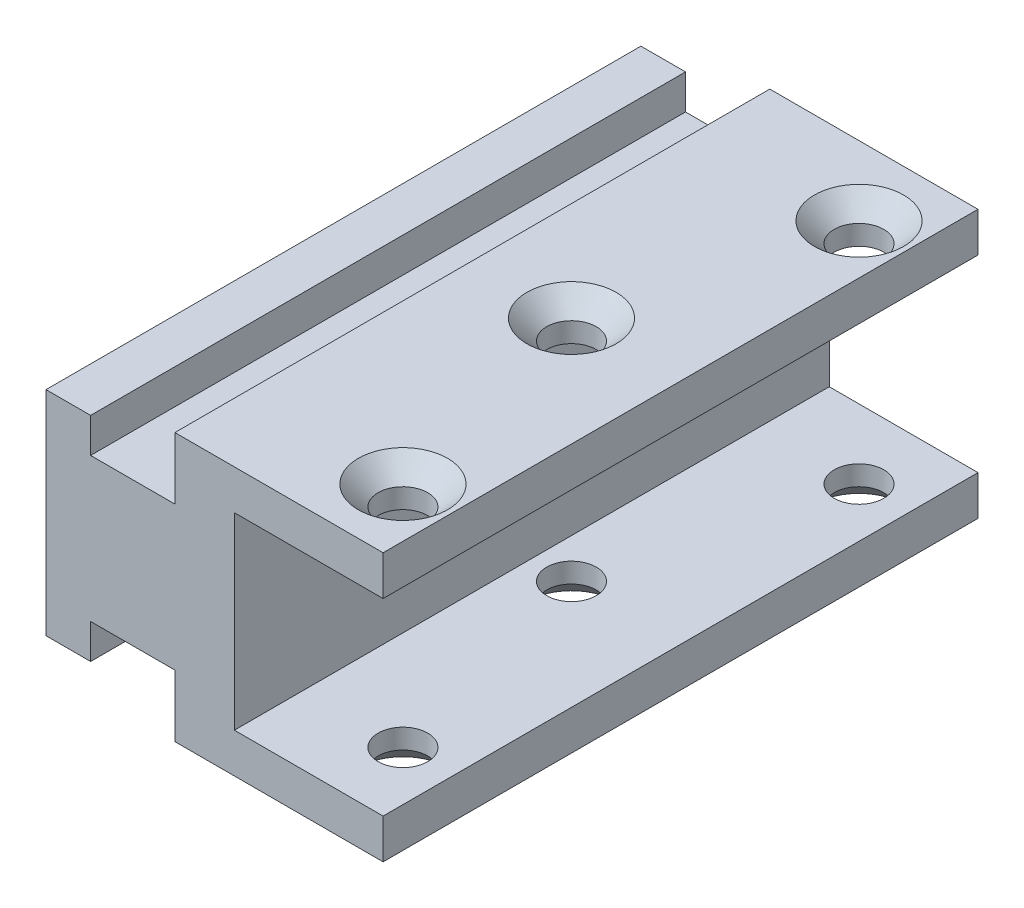
SolidWorks part; units mm, degrees
ref_plane "Front" through (0, 0, 0) normal (0, 0, 1) x (1, 0, 0)
ref_plane "Top" through (0, 0, 0) normal (0, 1, 0) x (1, 0, 0)
ref_plane "Right" through (0, 0, 0) normal (1, 0, 0) x (0, 0, -1)
sketch "Sketch1" plane through (0, 0, 0) normal (0, 0, 1) x (1, 0, 0)
  line L0 (0, -10.75) -> (0, 10.75)
  line L1 (0, 10.75) -> (4.5, 10.75)
  line L2 (4.5, 10.75) -> (4.5, 7.25)
  line L3 (4.5, 7.25) -> (13, 7.25)
  line L4 (13, 7.25) -> (13, 13.5)
  line L5 (13, 13.5) -> (34, 13.5)
  line L6 (34, 13.5) -> (34, 9.5)
  line L7 (34, 9.5) -> (19, 9.5)
  line L8 (19, 9.5) -> (19, -9.5)
  line L9 (0, 0) -> (52.8183, 0) construction
  line L10 (34, -9.5) -> (19, -9.5)
  line L11 (34, -13.5) -> (34, -9.5)
  line L12 (13, -13.5) -> (34, -13.5)
  line L13 (13, -7.25) -> (13, -13.5)
  line L14 (4.5, -7.25) -> (13, -7.25)
  line L15 (4.5, -10.75) -> (4.5, -7.25)
  line L16 (0, -10.75) -> (4.5, -10.75)
  point P13 (19, 0)
  dimension "D1" = 21.5
  dimension "D2" = 4.5
  dimension "D3" = 8.5
  dimension "D4" = 19
  dimension "D5" = 4
  dimension "D6" = 15
  dimension "D7" = 6
  dimension "D8" = 14.5
extrude "Boss-Extrude1" add sketch "Sketch1" along normal mid plane 60
sketch "Sketch2" plane through (0, -13.5, 0) normal (0, -1, 0) x (1, 0, 0)
  line L0 (0, 0) -> (47.8821, 0) construction
  line L1 (13, 30) -> (34, 30) construction
  line L2 (34, 30) -> (34, -30) construction
  circle A0 centre (29, 23) radius 2.5
  circle A1 centre (23, 0) radius 2.5
  circle A2 centre (29, -23) radius 2.5
  point P6 (0, 0)
  point P10 (20.6911, 0)
  point P13 (0, 0)
  point P15 (27.8757, 21.7645)
  dimension "D1" = 7
  dimension "D4" = 5
  dimension "D2" = 5
  dimension "D3" = 6
extrude "Cut-Extrude1" cut sketch "Sketch2" against normal through all
chamfer "Chamfer1" distance 2 angle 45 6 edges at (29, 13.5, -25.5) (23, 13.5, -2.5) (29, 13.5, 20.5) (29, -13.5, -25.5) (29, -13.5, 20.5) (23, -13.5, -2.5)
